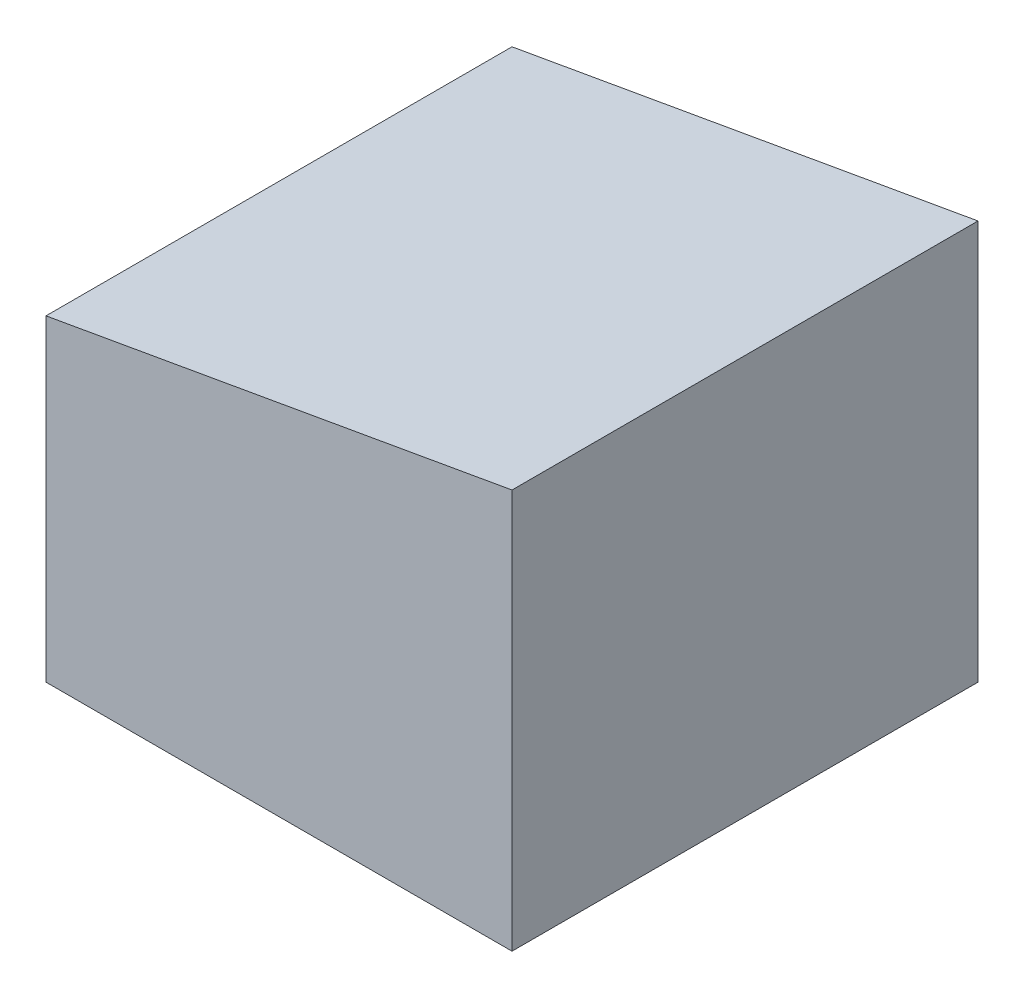
SolidWorks part; units mm, degrees
ref_plane "Front Plane" through (0, 0, 0) normal (0, 0, 1) x (1, 0, 0)
ref_plane "Top Plane" through (0, 0, 0) normal (0, 1, 0) x (1, 0, 0)
ref_plane "Right Plane" through (0, 0, 0) normal (1, 0, 0) x (0, 0, -1)
sketch "Sketch1" plane through (0, 0, 0) normal (0, 1, 0) x (1, 0, 0)
  line L1 (-44.45, -44.45) -> (44.45, -44.45)
  line L2 (-44.45, -44.45) -> (-44.45, 44.45)
  line L3 (-44.45, 44.45) -> (44.45, 44.45)
  line L4 (44.45, -44.45) -> (44.45, 44.45)
  line L5 (-44.45, -44.45) -> (44.45, 44.45) construction
  line L6 (-44.45, 44.45) -> (44.45, -44.45) construction
  point P0 (0, 0)
  dimension "D1" = 88.9
  dimension "D2" = 88.9
extrude "Boss-Extrude1" add sketch "Sketch1" along normal blind 76.2
sketch "Sketch2" plane through (0, 0, 44.45) normal (0, 0, 1) x (1, 0, 0)
  line L0 (44.45, 76.2) -> (-44.45, 60.5245)
  line L1 (-44.45, 76.2) -> (-44.45, 0) construction
  line L2 (-44.45, 60.5245) -> (-44.45, 76.2)
  line L3 (-44.45, 76.2) -> (44.45, 76.2)
  dimension "D1" = 10
extrude "Cut-Extrude1" cut sketch "Sketch2" against normal blind 135
